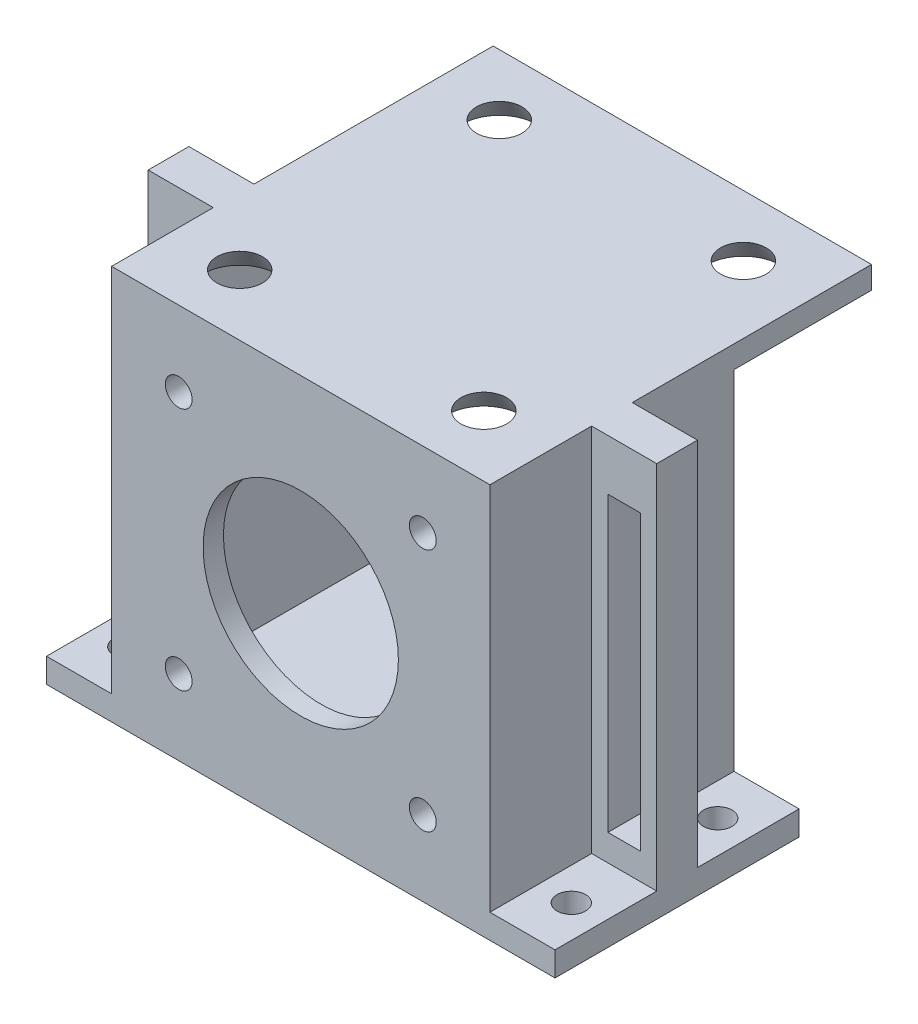
SolidWorks part; units mm, degrees
ref_plane "Front Plane" through (0, 0, 0) normal (0, 0, 1) x (1, 0, 0)
ref_plane "Top Plane" through (0, 0, 0) normal (0, 1, 0) x (1, 0, 0)
ref_plane "Right Plane" through (0, 0, 0) normal (1, 0, 0) x (0, 0, -1)
sketch "Sketch1" plane through (0, 0, 0) normal (0, 1, 0) x (1, 0, 0)
  line L0 (41, 30) -> (41, 0) construction
  line L1 (0, 0) -> (82, 0)
  line L2 (0, 0) -> (0, 30)
  line L3 (0, 30) -> (82, 30)
  line L4 (82, 0) -> (82, 30)
  line L5 (41, 15) -> (18, 15) construction
  line L6 (82, 14.3756) -> (74, 14.3756) construction
  line L7 (18, 30) -> (18, 0) construction
  line L8 (74, 30) -> (74, 0) construction
  line L9 (-7.5, 23.86) -> (-2.25, 23.86) construction
  line L10 (0, 30) -> (-12.5, 30)
  line L11 (0, 30) -> (0, 0)
  line L12 (0, 0) -> (-12.5, 0)
  line L13 (-12.5, 30) -> (-12.5, 0)
  line L14 (-7.5, 25.885) -> (-2.25, 25.885)
  line L15 (-7.5, 21.835) -> (-2.25, 21.835)
  line L17 (-7.4329, 4.985) -> (-2.1829, 4.985) construction
  line L18 (-7.4329, 7.01) -> (-2.1829, 7.01)
  line L19 (-7.4329, 2.96) -> (-2.1829, 2.96)
  arc A0 (-7.4329, 7.01) -> (-7.4329, 2.96) centre (-7.4329, 4.985) ccw
  circle A1 centre (4, 23.86) radius 2 construction
  circle A2 centre (4, 5) radius 2 construction
  circle A4 centre (78, 23.86) radius 2
  circle A5 centre (78, 5) radius 2
  arc A6 (-7.5, 25.885) -> (-7.5, 21.835) centre (-7.5, 23.86) ccw
  arc A7 (-2.25, 21.835) -> (-2.25, 25.885) centre (-2.25, 23.86) ccw
  arc A8 (-2.1829, 2.96) -> (-2.1829, 7.01) centre (-2.1829, 4.985) ccw
  point P29 (-4.875, 23.86)
  point P37 (-4.8079, 4.985)
  dimension "D3" = 4
  dimension "D7" = 4.05
  dimension "D14" = 5.25
  dimension "D15" = 4.05
  dimension "D16" = 18.875
  dimension "D1" = 82
  dimension "D2" = 30
  dimension "D4" = 4
  dimension "D5" = 4
  dimension "D6" = 12.5
  dimension "D8" = 18.86
  dimension "D9" = 5
  dimension "D10" = 23
  dimension "D11" = 8
  dimension "D12" = 5
  dimension "D13" = 5.25
extrude "Boss-Extrude1" add sketch "Sketch1" along normal blind 3 contours L1 L4 L3 L2 A4 A5 region at (40.6181, 0, -15.0059)
sketch "Sketch2" plane through (0, 3, 0) normal (0, 1, 0) x (1, 0, 0)
  line L0 (10, 40) -> (10, 0)
  line L4 (8, 40) -> (8, 0)
  line L5 (54.5, 40) -> (54.5, 0)
  line L6 (52.5, 40) -> (52.5, 0)
  line L7 (10, 2.5) -> (52.5, 2.5)
  line L9 (0, 0) -> (82, 0)
  line L10 (82, 0) -> (82, 30)
  line L11 (0, 0) -> (82, 0)
  line L12 (82, 30) -> (0, 30)
  line L13 (82, 30) -> (0, 30)
  line L14 (82, 0) -> (82, 30)
  line L15 (0, 30) -> (0, 0)
  line L16 (0, 30) -> (0, 0)
  dimension "D2" = 42.5
  dimension "D3" = 2
  dimension "D4" = 2
  dimension "D6" = 27.5
  dimension "D1" = 0
extrude "Boss-Extrude2" add sketch "Sketch2" along normal blind 42.5 contours L0 L4 | L0 L6 L7 | L5 L6 region at (31.25, 3, -1.25) region at (9, 3, -15) region at (53.5, 3, -15)
sketch "Sketch4" plane through (0, 0, 0) normal (0, 0, 1) x (1, 0, 0)
  line L0 (10, 45.5) -> (52.5, 3) construction
  line L1 (52.5, 45.5) -> (10, 3) construction
  line L6 (10, 3) -> (52.5, 3)
  line L7 (10, 45.5) -> (10, 3)
  line L8 (52.5, 45.5) -> (10, 45.5)
  line L9 (52.5, 3) -> (52.5, 45.5)
  line L10 (10, 3) -> (52.5, 3)
  line L11 (10, 45.5) -> (10, 3)
  line L12 (52.5, 45.5) -> (10, 45.5)
  line L13 (52.5, 3) -> (52.5, 45.5)
  circle A0 centre (31.25, 24.25) radius 12
  circle A1 centre (16.25, 39.25) radius 1.65
  circle A2 centre (16.25, 9.25) radius 1.65
  circle A3 centre (46.25, 9.25) radius 1.65
  circle A4 centre (46.25, 39.25) radius 1.65
  dimension "D2" = 24
  dimension "D3" = 3.3
  dimension "D4" = 30
  dimension "D1" = 0
extrude "Cut-Extrude2" cut sketch "Sketch4" against normal through all contours A0 | A2 | A1 | A4 | A3 region at (31.25, 24.25, 0)
sketch "Sketch7" plane through (0, 3, 0) normal (0, 1, 0) x (1, 0, 0)
  line L0 (54.5, 0) -> (82, 0) construction
  line L1 (82, 30) -> (62.5, 30)
  line L2 (82, 30) -> (82, 0)
  line L3 (82, 0) -> (62.5, 0)
  line L4 (62.5, 30) -> (62.5, 0)
  line L5 (54.5, 30) -> (54.5, 0) construction
  dimension "D1" = 8
extrude "Cut-Extrude4" cut sketch "Sketch7" against normal through all
sketch "Sketch8" plane through (0, 3, 0) normal (0, 1, 0) x (1, 0, 0)
  line L0 (8, 15) -> (0, 15) construction
  line L1 (8, 30) -> (8, 0) construction
  line L2 (0, 0) -> (0, 30) construction
  line L3 (31.25, 30) -> (31.25, 0) construction
  line L4 (10, 30) -> (52.5, 30) construction
  line L5 (54.5, 12.5) -> (62.5, 17.5) construction
  line L6 (8, 12.5) -> (0, 12.5)
  line L7 (8, 12.5) -> (8, 17.5)
  line L8 (8, 17.5) -> (0, 17.5)
  line L9 (0, 12.5) -> (0, 17.5)
  line L10 (8, 12.5) -> (0, 17.5) construction
  line L11 (8, 17.5) -> (0, 12.5) construction
  line L12 (54.5, 15) -> (62.5, 15) construction
  line L13 (54.5, 17.5) -> (62.5, 12.5) construction
  line L14 (62.5, 12.5) -> (62.5, 17.5)
  line L15 (54.5, 12.5) -> (54.5, 17.5)
  line L16 (54.5, 12.5) -> (62.5, 12.5)
  line L17 (54.5, 17.5) -> (62.5, 17.5)
  circle A0 centre (4, 24) radius 1.755
  circle A1 centre (4, 6) radius 1.755
  circle A2 centre (58.5, 6) radius 1.755
  circle A3 centre (58.5, 24) radius 1.755
  point P10 (4, 15)
  line M9 (8, 0) -> (8, 30)
  line M11 (0, 30) -> (0, 0)
  dimension "D2" = 3.51
  dimension "D1" = 5
  dimension "D3" = 4
  dimension "D4" = 9
extrude "Boss-Extrude3" add sketch "Sketch8" along normal up to surface (42.5 mm away) contours L8 L6 M9 M11 | L17 L15 L16 L14 region at (4, 3, -15) region at (58.5, 3, -15) up to face at (31.25, 45.5, -15.625)
extrude "Cut-Extrude5" cut sketch "Sketch8<3>" against normal through all contours A0 | A1 | A2 | A3
sketch "Sketch8<3>" plane through (0, 3, 0) normal (0, 1, 0) x (1, 0, 0) same geometry as "Sketch8"
sketch "Sketch9" plane through (0, 0, -17.5) normal (0, 0, -1) x (-1, 0, 0)
  line L0 (-58.5, 45.5) -> (-58.5, 0) construction
  line L1 (-54.5, 45.5) -> (-62.5, 45.5) construction
  line L2 (-31.25, 45.5) -> (-31.25, 3) construction
  line L3 (-10, 45.5) -> (-52.5, 45.5) construction
  line L4 (-10, 3) -> (-52.5, 3) construction
  line L5 (-4, 24.25) -> (-58.5, 24.25) construction
  line L6 (-56.5, 42.25) -> (-60.5, 42.25)
  line L7 (-56.5, 42.25) -> (-56.5, 6.25)
  line L8 (-56.5, 6.25) -> (-60.5, 6.25)
  line L9 (-60.5, 42.25) -> (-60.5, 6.25)
  line L10 (-56.5, 42.25) -> (-60.5, 6.25) construction
  line L11 (-56.5, 6.25) -> (-60.5, 42.25) construction
  line L12 (-6, 42.25) -> (-2, 42.25)
  line L13 (-4, 45.5) -> (-4, 0) construction
  line L14 (-2, 42.25) -> (-2, 6.25)
  line L15 (-6, 42.25) -> (-2, 6.25) construction
  line L16 (-6, 6.25) -> (-2, 42.25) construction
  line L17 (-6, 6.25) -> (-2, 6.25)
  line L18 (-6, 42.25) -> (-6, 6.25)
  point P10 (-58.5, 24.25)
  point P19 (-31.25, 24.25)
  dimension "D1" = 4
  dimension "D2" = 36
extrude "Cut-Extrude6" cut sketch "Sketch9" against normal through all
sketch "Sketch10" plane through (0, 45.5, 0) normal (0, 1, 0) x (1, 0, 0)
  line L0 (31.25, 30) -> (31.25, 2.5) construction
  line L1 (16.25, 39.4) -> (46.25, 39.4)
  line L2 (16.25, 39.4) -> (16.25, 7.5)
  line L3 (16.25, 7.5) -> (46.25, 7.5)
  line L4 (46.25, 39.4) -> (46.25, 7.5)
  line L6 (8, 0) -> (54.5, 0)
  line L7 (8, 0) -> (8, 46.9)
  line L8 (52.5, 30) -> (10, 30)
  line L9 (10, 30) -> (10, 2.5)
  line L10 (10, 2.5) -> (52.5, 2.5)
  line L11 (52.5, 2.5) -> (52.5, 30)
  line L12 (52.5, 30) -> (10, 30)
  line L13 (10, 30) -> (10, 2.5)
  line L14 (10, 2.5) -> (52.5, 2.5)
  line L15 (52.5, 2.5) -> (52.5, 30)
  line L16 (8, 46.9) -> (54.5, 46.9)
  line L17 (54.5, 0) -> (54.5, 46.9)
  circle A0 centre (16.25, 7.5) radius 2.5
  circle A1 centre (46.25, 7.5) radius 2.5
  circle A2 centre (31.25, 23.45) radius 2.51
  circle A7 centre (46.25, 39.4) radius 2.5
  circle A8 centre (16.25, 39.4) radius 2.5
  circle A9 centre (16.25, 7.5) radius 4.75
  circle A10 centre (46.25, 7.5) radius 4.75
  circle A11 centre (46.25, 39.4) radius 4.75
  circle A12 centre (16.25, 39.4) radius 4.75
  point P24 (54.5, 0)
  line M12 (10, 30) -> (8, 30)
  line M13 (8, 30) -> (8, 17.5)
  line M17 (8, 12.5) -> (8, 0)
  line M18 (8, 0) -> (54.5, 0)
  line M19 (54.5, 0) -> (54.5, 12.5)
  line M23 (54.5, 17.5) -> (54.5, 30)
  line M24 (54.5, 30) -> (52.5, 30)
  line M25 (52.5, 30) -> (52.5, 2.5)
  line M26 (52.5, 2.5) -> (10, 2.5)
  line M27 (10, 2.5) -> (10, 30)
  dimension "D8" = 5
  dimension "D9" = 5
  dimension "D10" = 5
  dimension "D11" = 5.02
  dimension "D14" = 9.5
  dimension "D15" = 9.5
  dimension "D16" = 9.5
  dimension "D17" = 9.5
  dimension "D1" = 0
  dimension "D2" = 15
  dimension "D3" = 31.9
  dimension "D4" = 30
  dimension "D5" = 15.95
  dimension "D6" = 5
  dimension "D7" = 6.25
  dimension "D12" = 7.5
extrude "Boss-Extrude4" add sketch "Sketch10" along normal blind 3 draft 33 contours A12 L1 A11 L4 L12 L17 L16 L7 L2 M24 M12 | L3 L0 L12 L4 A10 M26 M25 | L17 L14 L7 M19 M23 M24 M25 M26 M27 M12 M13 M17 M18 | L12 L0 A2 L3 A10 L4 | A12 L2 L12 L4 A11 L1 | L0 L12 L2 A9 L3 A2 | L0 L3 A9 L2 L12 L14 M27 | L0 A2 | A2 L0 region at (38.6419, 45.5, -19.1279) region at (31.25, 45.5, -34.3142) region at (23.8581, 45.5, -19.1279) region at (32.3153, 45.5, -23.45) region at (30.1847, 45.5, -23.45) region at (49.375, 45.5, -29.6525) region at (31.25, 45.5, -40.6764) region at (15.9025, 45.5, -21.125) region at (53.5, 45.5, -29.4466) draft outward yes
sketch "Sketch12" plane through (0, 45.5, 0) normal (0, 1, 0) x (1, 0, 0)
  line L4 (0, 12.5) -> (8, 12.5)
  line L5 (8, 12.5) -> (8, 17.5)
  line L6 (8, 17.5) -> (0, 17.5)
  line L7 (0, 17.5) -> (0, 12.5)
  line L8 (0, 12.5) -> (8, 12.5)
  line L9 (8, 12.5) -> (8, 17.5)
  line L10 (8, 17.5) -> (0, 17.5)
  line L11 (0, 17.5) -> (0, 12.5)
  line L12 (54.5, 17.5) -> (54.5, 12.5)
  line L13 (54.5, 12.5) -> (62.5, 12.5)
  line L14 (62.5, 12.5) -> (62.5, 17.5)
  line L15 (62.5, 17.5) -> (54.5, 17.5)
  line L16 (54.5, 17.5) -> (54.5, 12.5)
  line L17 (54.5, 12.5) -> (62.5, 12.5)
  line L18 (62.5, 12.5) -> (62.5, 17.5)
  line L19 (62.5, 17.5) -> (54.5, 17.5)
  dimension "D1" = 0
  dimension "D2" = 0
extrude "Boss-Extrude6" add sketch "Sketch12" along normal up to surface (3 mm away) up to face at (46.25, 48.5, -4.6982)
sketch "Sketch13" plane through (0, 48.5, 0) normal (0, 1, 0) x (1, 0, 0)
  line L0 (56.4482, 17.5) -> (54.5, 17.5) construction
  line L1 (54.5, 17.5) -> (54.5, 30) construction
  line L2 (54.5, 30) -> (54.5, 46.9) construction
  line L3 (56.4482, 48.8482) -> (56.4482, 17.5) construction
  line L4 (54.5, 12.5) -> (56.4482, 12.5) construction
  line L5 (56.4482, 12.5) -> (56.4482, -1.9482) construction
  line L6 (54.5, 0) -> (54.5, 12.5) construction
  line L7 (8, 0) -> (54.5, 0) construction
  line L8 (56.4482, -1.9482) -> (6.0518, -1.9482) construction
  line L9 (54.5, 46.9) -> (8, 46.9) construction
  line L10 (6.0518, 48.8482) -> (56.4482, 48.8482) construction
  line L11 (8, 30) -> (8, 17.5) construction
  line L12 (8, 17.5) -> (6.0518, 17.5) construction
  line L13 (6.0518, 17.5) -> (6.0518, 48.8482) construction
  line L14 (8, 46.9) -> (8, 30) construction
  line L15 (6.0518, -1.9482) -> (6.0518, 12.5) construction
  line L16 (6.0518, 12.5) -> (8, 12.5) construction
  line L17 (8, 12.5) -> (8, 0) construction
  line L18 (56.4482, 17.5) -> (54.5, 17.5)
  line L19 (54.5, 17.5) -> (54.5, 30)
  line L20 (54.5, 30) -> (54.5, 46.9)
  line L21 (56.4482, 48.8482) -> (56.4482, 17.5)
  line L22 (54.5, 12.5) -> (56.4482, 12.5)
  line L23 (56.4482, 12.5) -> (56.4482, -1.9482)
  line L24 (54.5, 0) -> (54.5, 12.5)
  line L25 (8, 0) -> (54.5, 0)
  line L26 (56.4482, -1.9482) -> (6.0518, -1.9482)
  line L27 (54.5, 46.9) -> (8, 46.9)
  line L28 (6.0518, 48.8482) -> (56.4482, 48.8482)
  line L29 (8, 30) -> (8, 17.5)
  line L30 (8, 17.5) -> (6.0518, 17.5)
  line L31 (6.0518, 17.5) -> (6.0518, 48.8482)
  line L32 (8, 46.9) -> (8, 30)
  line L33 (6.0518, -1.9482) -> (6.0518, 12.5)
  line L34 (6.0518, 12.5) -> (8, 12.5)
  line L35 (8, 12.5) -> (8, 0)
extrude "Cut-Extrude7" cut sketch "Sketch13" against normal up to surface (3 mm away) up to face at (46.25, 45.5, -2.75)
sketch "Sketch15" plane through (0, 45.5, 0) normal (0, -1, 0) x (1, 0, 0)
  line L8 (10, -2.5) -> (10, -30)
  line L9 (10, -30) -> (8, -30)
  line L10 (8, -30) -> (8, -46.9)
  line L11 (8, -46.9) -> (54.5, -46.9)
  line L12 (54.5, -46.9) -> (54.5, -30)
  line L13 (54.5, -30) -> (52.5, -30)
  line L14 (52.5, -30) -> (52.5, -2.5)
  line L15 (52.5, -2.5) -> (10, -2.5)
  line L16 (10, -2.5) -> (10, -30)
  line L17 (10, -30) -> (8, -30)
  line L18 (8, -30) -> (8, -46.9)
  line L19 (8, -46.9) -> (54.5, -46.9)
  line L20 (54.5, -46.9) -> (54.5, -30)
  line L21 (54.5, -30) -> (52.5, -30)
  line L22 (52.5, -30) -> (52.5, -2.5)
  line L23 (52.5, -2.5) -> (10, -2.5)
  dimension "D1" = 0
extrude "Cut-Extrude8" cut sketch "Sketch15" against normal blind 0.25
